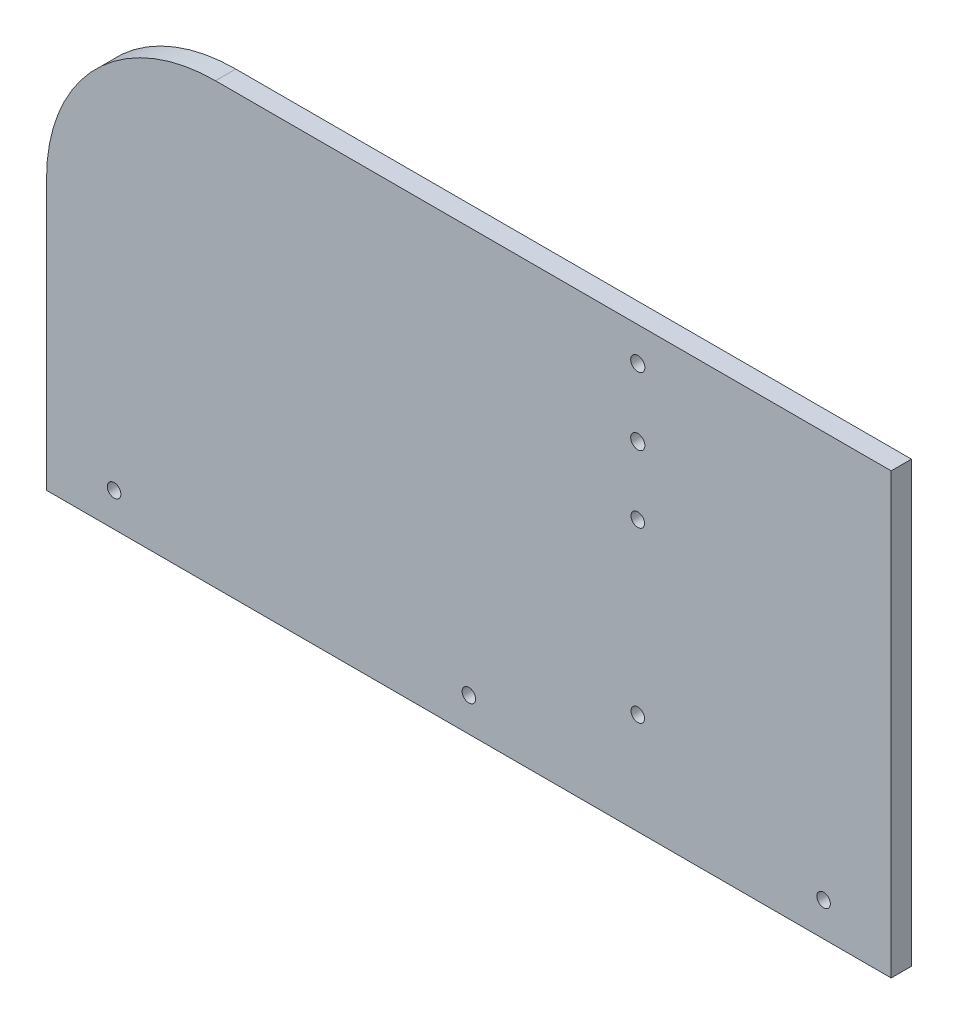
SolidWorks part; units mm, degrees
ref_plane "Plano frontal" through (0, 0, 0) normal (0, 0, 1) x (1, 0, 0)
ref_plane "Plano superior" through (0, 0, 0) normal (0, 1, 0) x (1, 0, 0)
ref_plane "Plano direito" through (0, 0, 0) normal (1, 0, 0) x (0, 0, -1)
sketch "Esboço1" plane through (0, 0, 0) normal (0, 0, 1) x (1, 0, 0)
  line L1 (-125, 65) -> (125, 65)
  line L2 (-125, 65) -> (-125, -65)
  line L3 (-125, -65) -> (125, -65)
  line L4 (125, 65) -> (125, -65)
  line L5 (-125, 65) -> (125, -65) construction
  line L6 (-125, -65) -> (125, 65) construction
  point P0 (0, 0)
  dimension "D1" = 250
  dimension "D2" = 130
extrude "Ressalto-extrusão1" add sketch "Esboço1" along normal blind 6
fillet "Filete1" radius 50 1 edges at (-125, 65, 3)
sketch "Esboço2" plane through (0, 0, 0) normal (0, 0, -1) x (-1, 0, 0)
  line L2 (125, -55) -> (-125, -55)
  line L3 (125, -55) -> (-125, -55) construction
  line L7 (105, 15) -> (105, -65)
  line L8 (105, 15) -> (105, -65) construction
  line L10 (-105, -65) -> (-105, 65)
  line L11 (-105, -65) -> (-105, 65) construction
  circle A0 centre (0, -55) radius 2
  circle A1 centre (105, -55) radius 2
  circle A2 centre (-105, -55) radius 2
  dimension "D4" = 4
  dimension "D1" = 10
  dimension "D2" = 20
  dimension "D3" = 20
extrude "Corte-extrusão1" cut sketch "Esboço2" against normal up to surface (6 mm away) up to face at (-17.0711, 5.0711, 6)
sketch "Esboço3" plane through (0, 0, 0) normal (0, 0, -1) x (-1, 0, 0)
  circle A0 centre (-50, 55) radius 2.1 construction
  circle A1 centre (-50, 35) radius 2.1 construction
  circle A2 centre (-50, 55) radius 2.1
  circle A3 centre (-50, 35) radius 2.1
extrude "Corte-extrusão2" cut sketch "Esboço3" against normal up to surface (6 mm away) up to face at (-103, -55, 6)
sketch "Esboço4" plane through (0, 0, 0) normal (0, 0, -1) x (-1, 0, 0)
  line L0 (-50, 15) -> (-50, -35) construction
  line L1 (-50, -34.55) -> (-50, -55.45) construction
  line L2 (-50, -10) -> (-42.9462, -10) construction
  line L3 (-39, -10) -> (-61, -10) construction
  circle A0 centre (-50, 15) radius 2
  circle A1 centre (-50, -35) radius 2
  dimension "D1" = 4
  dimension "D2" = 50
extrude "Corte-extrusão3" cut sketch "Esboço4" against normal up to surface (6 mm away) up to face at (52.1, 55, 6)
